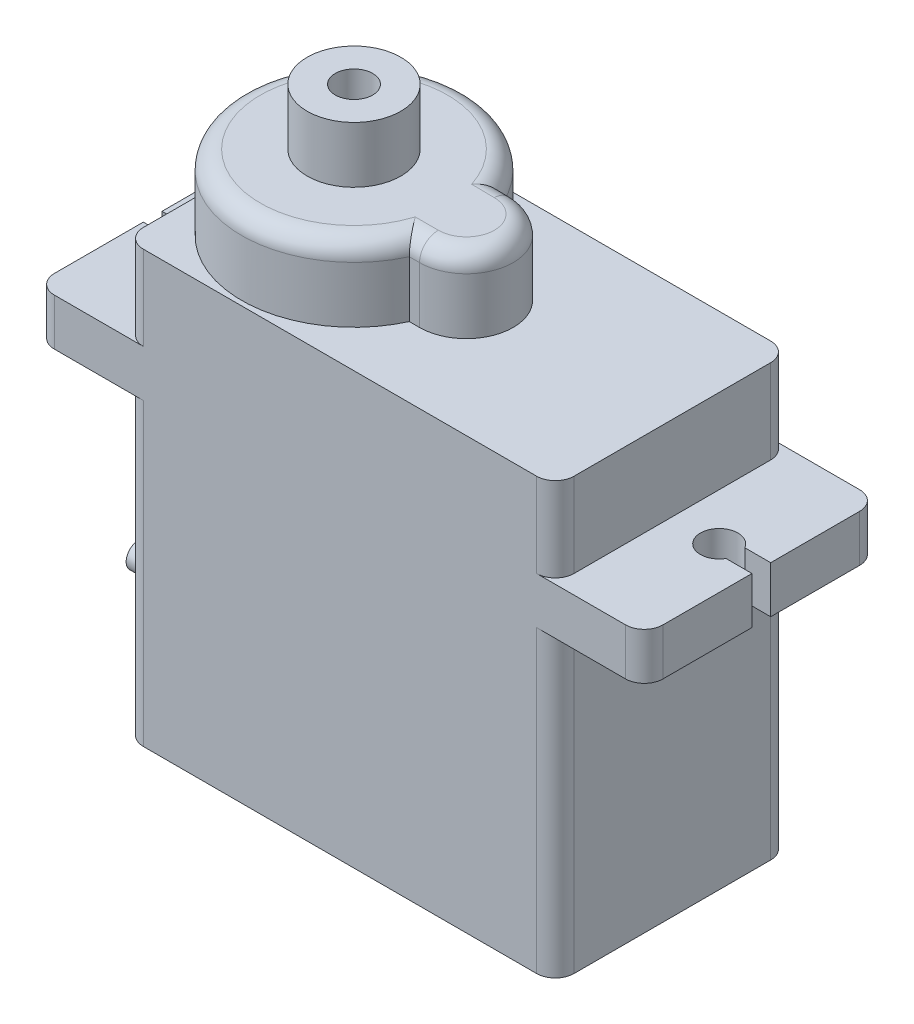
SolidWorks part; units mm, degrees
ref_plane "Front Plane" through (0, 0, 0) normal (0, 0, 1) x (1, 0, 0)
ref_plane "Top Plane" through (0, 0, 0) normal (0, 1, 0) x (1, 0, 0)
ref_plane "Right Plane" through (0, 0, 0) normal (1, 0, 0) x (0, 0, -1)
sketch "Sketch1" plane through (0, 0, 0) normal (0, 1, 0) x (1, 0, 0)
  line L1 (-11.5, 6.25) -> (11.5, 6.25)
  line L2 (-11.5, 6.25) -> (-11.5, -6.25)
  line L3 (-11.5, -6.25) -> (11.5, -6.25)
  line L4 (11.5, 6.25) -> (11.5, -6.25)
  line L5 (-11.5, 6.25) -> (11.5, -6.25) construction
  line L6 (-11.5, -6.25) -> (11.5, 6.25) construction
  point P0 (0, 0)
  dimension "D1" = 12.5
  dimension "D2" = 23
extrude "Boss-Extrude1" add sketch "Sketch1" along normal blind 16
sketch "Sketch2" plane through (0, 16, 0) normal (0, 1, 0) x (1, 0, 0)
  line L0 (-11.5, -6.25) -> (11.5, -6.25) construction
  line L1 (-16.25, 6.25) -> (16.25, 6.25)
  line L2 (-16.25, 6.25) -> (-16.25, -6.25)
  line L3 (-16.25, -6.25) -> (16.25, -6.25)
  line L4 (16.25, 6.25) -> (16.25, -6.25)
  line L5 (-16.25, 6.25) -> (16.25, -6.25) construction
  line L6 (-16.25, -6.25) -> (16.25, 6.25) construction
  point P0 (0, 0)
  dimension "D1" = 32.5
extrude "Boss-Extrude2" add sketch "Sketch2" along normal blind 2.5
sketch "Sketch3" plane through (0, 18.5, 0) normal (0, 1, 0) x (1, 0, 0)
  line L0 (-16.25, -6.25) -> (16.25, -6.25) construction
  line L1 (-11.5, 6.25) -> (11.5, 6.25)
  line L2 (-11.5, 6.25) -> (-11.5, -6.25)
  line L3 (-11.5, -6.25) -> (11.5, -6.25)
  line L4 (11.5, 6.25) -> (11.5, -6.25)
  line L5 (-11.5, 6.25) -> (11.5, -6.25) construction
  line L6 (-11.5, -6.25) -> (11.5, 6.25) construction
  point P0 (0, 0)
  dimension "D1" = 23
extrude "Boss-Extrude3" add sketch "Sketch3" along normal blind 4.5
sketch "Sketch4" plane through (0, 23, 0) normal (0, 1, 0) x (1, 0, 0)
  line L0 (-5.5, 0) -> (0, 0) construction
  line L3 (-11.5, 6.25) -> (-11.5, -6.25) construction
  line L4 (0.5, 2.5) -> (-0.0492, 2.5078)
  line L5 (0.5, -2.5) -> (-0.0456, -2.5)
  arc A0 (-0.0492, 2.5078) -> (-0.0456, -2.5) centre (-5.5, 0) ccw
  arc A1 (0.5, -2.5) -> (0.5, 2.5) centre (0.5, 0) ccw
  dimension "D1" = 12
  dimension "D2" = 5
extrude "Boss-Extrude4" add sketch "Sketch4" along normal blind 4
sketch "Sketch5" plane through (0, 27, 0) normal (0, 1, 0) x (1, 0, 0)
  circle A0 centre (-5.5, 0) radius 1
  circle A1 centre (-5.5, 0) radius 2.5
  dimension "D1" = 5
  dimension "D2" = 2
extrude "Boss-Extrude5" add sketch "Sketch5" along normal blind 3
fillet "Fillet1" radius 1 16 edges at (0.2254, 27, -2.5039) (3, 27, 0) (11.5, 8, -6.25) (11.5, 8, 6.25) (16.25, 17.25, -6.25) (16.25, 17.25, 6.25) (11.5, 20.75, -6.25) (11.5, 20.75, 6.25) (-11.5, 8, -6.25) (-11.5, 20.75, -6.25) (-16.25, 17.25, -6.25) (-16.25, 17.25, 6.25) (-11.5, 8, 6.25) (-11.5, 20.75, 6.25) (0.2272, 27, 2.5) (-11.5, 27, 0.0043)
sketch "Sketch6" plane through (0, 18.5, 0) normal (0, 1, 0) x (1, 0, 0)
  line L0 (-14, 0) -> (14, 0) construction
  line L1 (-16.25, 5.25) -> (-16.25, -5.25) construction
  line L2 (-16.25, 0.5) -> (-14.866, 0.5)
  line L3 (-16.25, 0.5) -> (-16.25, -0.5)
  line L4 (-16.25, -0.5) -> (-14.866, -0.5)
  line L6 (16.25, -5.25) -> (16.25, 5.25) construction
  line L7 (14.866, 0.5) -> (16.25, 0.5)
  line L9 (14.866, -0.5) -> (16.25, -0.5)
  line L10 (16.25, 0.5) -> (16.25, -0.5)
  arc A0 (-14.866, -0.5) -> (-14.866, 0.5) centre (-14, 0) ccw
  arc A1 (14.866, 0.5) -> (14.866, -0.5) centre (14, 0) ccw
  point P16 (0, 0)
  dimension "D2" = 2
  dimension "D1" = 28
  dimension "D3" = 1
  dimension "D4" = 1
extrude "Cut-Extrude1" cut sketch "Sketch6" against normal through all
sketch "Sketch7" plane through (-11.5, 0, 0) normal (-1, 0, 0) x (0, 0, 1)
  line L0 (-1.5, 4) -> (1.5, 4) construction
  line L1 (0, 0) -> (0, 4) construction
  circle A0 centre (0, 4) radius 0.6667
  circle A1 centre (1.5, 4) radius 0.6667
  circle A2 centre (-1.5, 4) radius 0.6667
  dimension "D3" = 1.3333
  dimension "D1" = 4
  dimension "D2" = 3
extrude "Boss-Extrude7" add sketch "Sketch7" along normal blind 4
